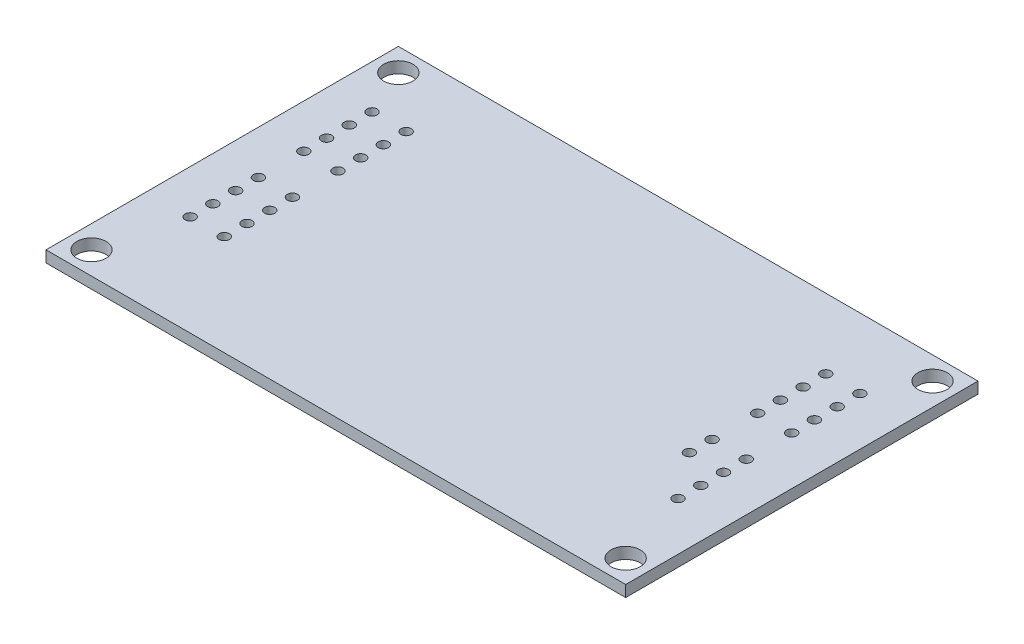
SolidWorks part; units mm, degrees
material "6061-T6 (SS)"
ref_plane "Front Plane" through (0, 0, 0) normal (0, 0, 1) x (1, 0, 0)
ref_plane "Top Plane" through (0, 0, 0) normal (0, 1, 0) x (1, 0, 0)
ref_plane "Right Plane" through (0, 0, 0) normal (1, 0, 0) x (0, 0, -1)
sketch "Sketch1" plane through (0, 0, 0) normal (0, 1, 0) x (1, 0, 0)
  line L1 (-32.385, -19.685) -> (32.385, -19.685)
  line L2 (-32.385, -19.685) -> (-32.385, 19.685)
  line L3 (-32.385, 19.685) -> (32.385, 19.685)
  line L4 (32.385, -19.685) -> (32.385, 19.685)
  line L5 (-32.385, -19.685) -> (32.385, 19.685) construction
  line L6 (-32.385, 19.685) -> (32.385, -19.685) construction
  point P0 (0, 0)
  dimension "D1" = 64.77
  dimension "D2" = 39.37
extrude "Boss-Extrude1" add sketch "Sketch1" along normal blind 1.27
hole_wizard "#4 Clearance Hole1" positions "Sketch2" profile "Sketch3" hole size "#4" standard "ANSI Inch"
sketch "Sketch2" plane through (0, 1.27, 0) normal (0, 1, 0) x (1, 0, 0)
  line L0 (-32.385, -19.685) -> (32.385, -19.685) construction
  line L1 (-32.385, 19.685) -> (-32.385, -19.685) construction
  line L2 (32.385, 19.685) -> (-32.385, 19.685) construction
  line L3 (32.385, -19.685) -> (32.385, 19.685) construction
  point P0 (-29.845, 17.145)
  point P2 (-29.845, -17.145)
  point P4 (29.845, -17.145)
  point P6 (29.845, 17.145)
  dimension "D1" = 2.54
  dimension "D2" = 2.54
  dimension "D3" = 2.54
  dimension "D4" = 2.54
sketch "Sketch3" plane through (-29.845, 1.27, -17.145) normal (1, 0, 0) x (0, 0, 1)
  line L0 (0, 0) -> (0, 8.5752)
  line L1 (0, 8.5752) -> (1.6319, 7.5946)
  line L2 (1.6319, 7.5946) -> (1.6319, 0)
  line L5 (1.6319, 0) -> (0, 0)
  line L10 (0, 8.5752) -> (-1.632, 7.5946) construction
  line L11 (0, -6.35) -> (0, 107.95) construction
  dimension "Hole Dia." = 3.2639
  dimension "Hole Depth" = 7.5946
  dimension "Drill Angle" = 118
sketch "Sketch4" plane through (0, 1.27, 0) normal (0, 1, 0) x (1, 0, 0)
  circle A0 centre (-27.5168, 11.8757) radius 0.5715
  point P2 (-27.5168, 11.8757)
  dimension "D1" = 1.143
extrude "Cut-Extrude1" cut sketch "Sketch4" against normal through all
pattern_linear "LPattern1" count 4 spacing 2.54 along (0, 0, 1) of "Cut-Extrude1"
pattern_linear "LPattern2" count 2 spacing 3.81 along (1, 0, 0) count 2 spacing 12.7 along (0, 0, 1) of "LPattern1"
sketch "Sketch5" plane through (0, 1.27, 0) normal (0, 1, 0) x (1, 0, 0)
  circle A0 centre (26.997, 11.8757) radius 0.5715
  circle A1 centre (-23.7068, 11.8757) radius 0.5715 construction
  point P4 (-23.7068, 11.8757)
  point P5 (0, 0)
extrude "Cut-Extrude2" cut sketch "Sketch5" against normal through all
pattern_linear "LPattern3" count 4 spacing 2.54 along (0, 0, 1) of "Cut-Extrude2"
pattern_linear "LPattern4" count 2 spacing 12.7 along (0, 0, 1) count 2 spacing 3.81 along (-1, 0, 0) skipping (1, 1) of "LPattern3"
sketch "Sketch6" plane through (0, 1.27, 0) normal (0, 1, 0) x (1, 0, 0)
  circle A0 centre (23.187, -0.8243) radius 0.5715
  circle A1 centre (23.187, -3.3643) radius 0.5715
  circle A2 centre (26.997, -0.8243) radius 0.5715 construction
  point P6 (26.997, -0.8243)
  point P7 (26.997, -3.3643)
  point P9 (23.187, 4.2557)
  point P11 (0, 0)
  point P13 (0, 0)
  point P14 (0, 0)
extrude "Cut-Extrude3" cut sketch "Sketch6" against normal through all
